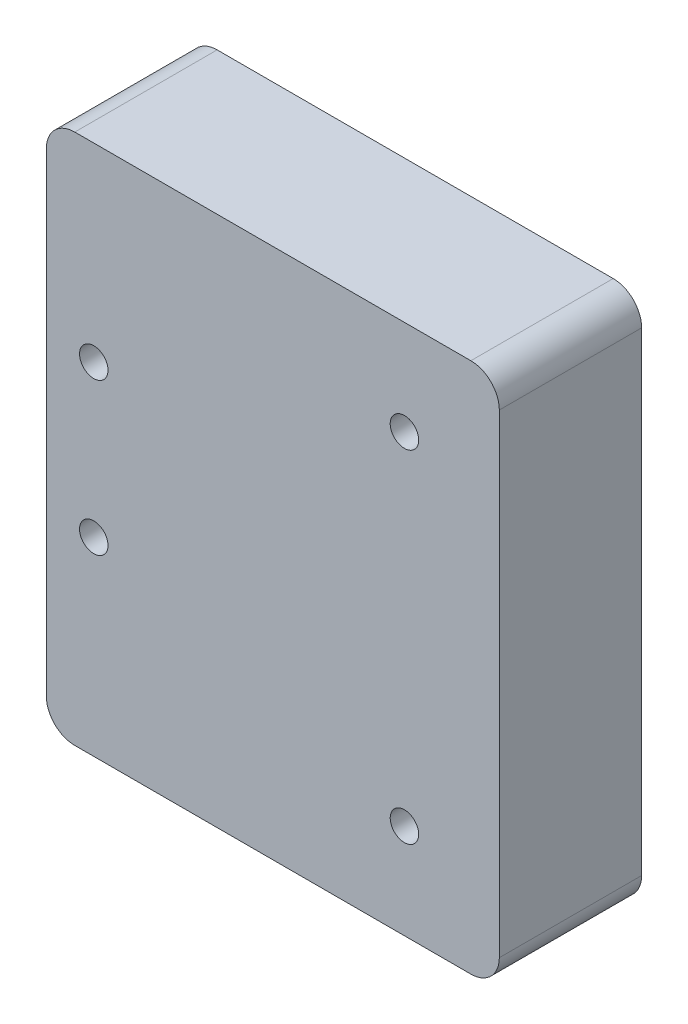
SolidWorks part; units mm, degrees
ref_plane "Plan de face" through (0, 0, 0) normal (0, 0, 1) x (1, 0, 0)
ref_plane "Plan de dessus" through (0, 0, 0) normal (0, 1, 0) x (1, 0, 0)
ref_plane "Plan de droite" through (0, 0, 0) normal (1, 0, 0) x (0, 0, -1)
sketch "Esquisse1" plane through (0, 0, 0) normal (0, 0, 1) x (1, 0, 0)
  line L1 (0, 0) -> (60, 0)
  line L2 (0, 0) -> (0, 60)
  line L3 (0, 60) -> (60, 60)
  line L4 (60, 0) -> (60, 60)
  dimension "D1" = 60
  dimension "D2" = 60
extrude "Boss.-Extru.1" add sketch "Esquisse1" along normal blind 15
sketch "Esquisse2" plane through (0, 0, 0) normal (0, 0, 1) x (1, 0, 0)
  line L0 (0, 60) -> (0, 0) construction
  circle A0 centre (10, 34.4866) radius 4.3
  circle A1 centre (10, 18.1866) radius 4.3
  circle A2 centre (24.645, 26.3366) radius 5
  dimension "D2" = 10
  dimension "D3" = 8.6
  dimension "D4" = 8.6
  dimension "D5" = 16.3
  dimension "D6" = 16.76
  dimension "D7" = 16.76
  dimension "D10" = 10
  dimension "D11" = 10
extrude "Enlèv. mat.-Extru.1" cut sketch "Esquisse2" along normal blind 8
sketch "Esquisse4" plane through (0, 0, 0) normal (0, 0, 1) x (1, 0, 0)
  line L0 (0, 0) -> (60, 0) construction
  line L1 (60, 60) -> (47.7399, 60)
  line L2 (60, 60) -> (60, 0)
  line L3 (60, 0) -> (47.7399, 0)
  line L4 (47.7399, 60) -> (47.7399, 0)
extrude "Enlèv. mat.-Extru.2" cut sketch "Esquisse4" along normal through all
sketch "Esquisse5" plane through (0, 0, 0) normal (1, 0, 0) x (0, 0, -1)
  line L2 (-15, 0) -> (0, 0) construction
  circle A0 centre (-7.78, 8) radius 4
  circle A1 centre (-7.78, 48) radius 4
  dimension "D1" = 8
  dimension "D2" = 8
  dimension "D3" = 40
  dimension "D4" = 8
extrude "Enlèv. mat.-Extru.3" cut sketch "Esquisse5" along normal blind 8
sketch "Esquisse6" plane through (0, 0, 0) normal (0, 0, -1) x (-1, 0, 0)
  line L0 (0, 60) -> (0, 0) construction
  line L1 (-47.7399, 55.984) -> (0, 55.984)
  line L2 (-47.7399, 55.984) -> (-47.7399, 60)
  line L3 (-47.7399, 60) -> (0, 60)
  line L4 (0, 55.984) -> (0, 60)
  line L5 (-47.7399, 60) -> (-47.7399, 0) construction
extrude "Enlèv. mat.-Extru.4" cut sketch "Esquisse6" against normal through all
fillet "Congé1" radius 3 4 edges at (47.7399, 0, 7.5) (47.7399, 55.984, 7.5) (0, 55.984, 7.5) (0, 0, 7.5)
sketch "Esquisse7" plane through (0, 0, 15) normal (0, 0, 1) x (1, 0, 0)
  line L0 (44.7399, 55.984) -> (3, 55.984) construction
  line L1 (47.7399, 52.984) -> (47.7399, 3) construction
  line L2 (3, 0) -> (44.7399, 0) construction
  line L3 (0, 52.984) -> (0, 3) construction
  circle A0 centre (37.7399, 45.984) radius 1.5
  circle A1 centre (37.7399, 10) radius 1.5
  circle A2 centre (5, 20) radius 1.5
  circle A3 centre (5, 35.984) radius 1.5
  dimension "D1" = 3
  dimension "D2" = 3
  dimension "D3" = 3
  dimension "D4" = 3
  dimension "D6" = 10
  dimension "D7" = 10
  dimension "D8" = 10
  dimension "D9" = 5
  dimension "D10" = 5
  dimension "D11" = 20
  dimension "D12" = 20
  dimension "D5" = 10
extrude "Enlèv. mat.-Extru.5" cut sketch "Esquisse7" against normal blind 5
